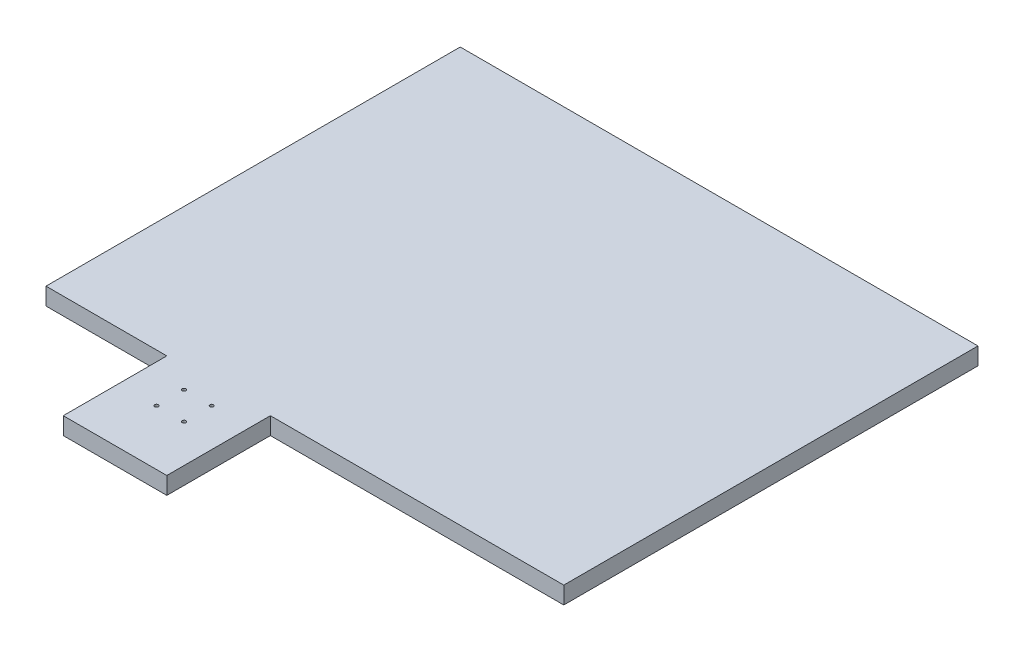
SolidWorks part; units mm, degrees
ref_plane "前基準面" through (0, 0, 0) normal (0, 0, 1) x (1, 0, 0)
ref_plane "上基準面" through (0, 0, 0) normal (0, 1, 0) x (1, 0, 0)
ref_plane "右基準面" through (0, 0, 0) normal (1, 0, 0) x (0, 0, -1)
sketch "草圖1" plane through (0, 0, 0) normal (0, 1, 0) x (1, 0, 0)
  line L0 (-50, -987.0204) -> (-50, 49012.9796) construction
  line L1 (-150, -120) -> (-80, -120)
  line L2 (-150, -120) -> (-150, 120)
  line L3 (-150, 120) -> (150, 120)
  line L4 (150, -120) -> (150, 120)
  line L5 (-150, -120) -> (150, 120) construction
  line L6 (-150, 120) -> (150, -120) construction
  line L7 (-80, -120) -> (-80, -180)
  line L8 (-80, -180) -> (-20, -180)
  line L9 (-20, -180) -> (-20, -120)
  line L10 (-20, -120) -> (150, -120)
  point P0 (0, 0)
  point P10 (-50, -180)
  dimension "D1" = 300
  dimension "D2" = 240
  dimension "D3" = 200
  dimension "D4" = 60
  dimension "D5" = 60
extrude "填料-伸長1" add sketch "草圖1" along normal blind 10
sketch "草圖2" plane through (0, 0, 0) normal (0, -1, 0) x (1, 0, 0)
  line L0 (-50, -820) -> (-50, 49180) construction
  line L1 (-80, 180) -> (-20, 180) construction
  line L2 (-1080, 140) -> (48920, 140) construction
  line L4 (-150, 120) -> (-80, 120) construction
  line L6 (-40, 150) -> (-60, 150)
  line L7 (-40, 150) -> (-40, 130)
  line L8 (-40, 130) -> (-60, 130)
  line L9 (-60, 150) -> (-60, 130)
  line L10 (-40, 150) -> (-60, 130) construction
  line L11 (-40, 130) -> (-60, 150) construction
  circle A0 centre (-58, 132) radius 1.05
  circle A1 centre (-58, 148) radius 1.05
  circle A2 centre (-42, 148) radius 1.05
  circle A3 centre (-42, 132) radius 1.05
  point P5 (-50, 180)
  point P20 (-50, 140)
  dimension "D1" = 2.1
  dimension "D2" = 20
  dimension "D3" = 8
  dimension "D4" = 8
  dimension "D5" = 20
  dimension "D6" = 20
extrude "除料-伸長2" cut sketch "草圖2" against normal blind 8 contours L6 L9 L8 L7 A1 A0 A2 A3 region at (-50, 0, 140)
extrude "除料-伸長3" cut sketch "草圖2<3>" against normal through all contours A3 | A0 | A1 | A2 region at (-58, 0, 132) region at (-58, 0, 148) region at (-42, 0, 148) region at (-42, 0, 132)
sketch "草圖2<3>" plane through (0, 0, 0) normal (0, -1, 0) x (1, 0, 0) same geometry as "草圖2"
